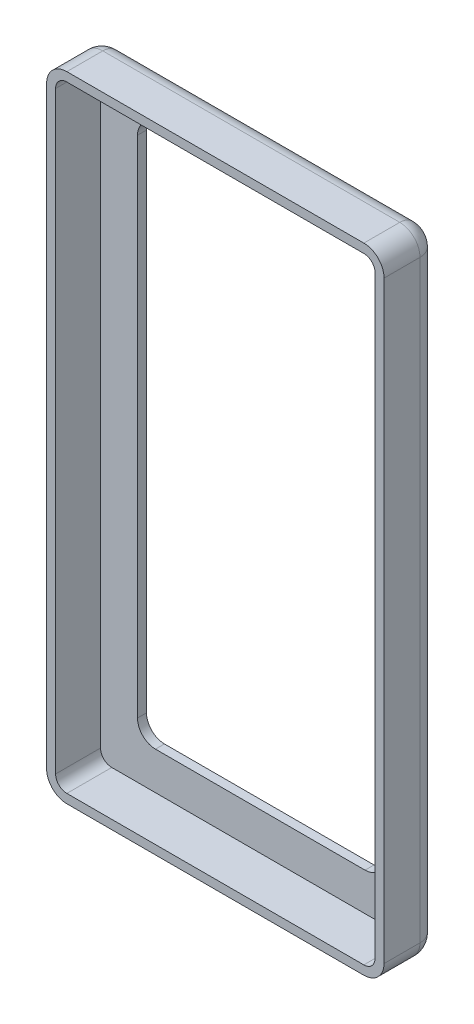
SolidWorks part; units mm, degrees
material "Plastique personnalisé"
ref_plane "Plan de face" through (0, 0, 0) normal (0, 0, 1) x (1, 0, 0)
ref_plane "Plan de dessus" through (0, 0, 0) normal (0, 1, 0) x (1, 0, 0)
ref_plane "Plan de droite" through (0, 0, 0) normal (1, 0, 0) x (0, 0, -1)
sketch "Esquisse1" plane through (0, 0, 0) normal (0, 0, 1) x (1, 0, 0)
  line L0 (-33.5062, 69.5614) -> (42.7461, 69.5614) construction
  line L1 (35.0738, 14.3164) -> (35.0738, 71.5291) construction
  line L2 (-36.0462, -49.8186) -> (-36.0462, -71.5291) construction
  line L3 (-19.7068, -67.5986) -> (-42.7461, -67.5986) construction
  line L4 (-33.5462, -67.5986) -> (32.5738, -67.5986)
  line L5 (-36.0462, -65.0986) -> (-36.0462, 67.0614)
  line L6 (-33.5462, 69.5614) -> (32.5738, 69.5614)
  line L7 (35.0738, -65.0986) -> (35.0738, 67.0614)
  arc A4 (32.5738, -67.5986) -> (35.0738, -65.0986) centre (32.5738, -65.0986) ccw
  arc A5 (-33.5462, -67.5986) -> (-36.0462, -65.0986) centre (-33.5462, -65.0986) cw
  arc A6 (-36.0462, 67.0614) -> (-33.5462, 69.5614) centre (-33.5462, 67.0614) cw
  arc A7 (32.5738, 69.5614) -> (35.0738, 67.0614) centre (32.5738, 67.0614) cw
extrude "Boss.-Extru.1" add sketch "Esquisse1" along normal blind 10
shell "Coque1" thickness 2 removed face at (-0.4862, 0.9814, 10) outward yes
fillet "Congé1" radius 4 8 edges at (37.0738, 0.9814, -2) (35.7558, -68.2806, -2) (-0.4862, -69.5986, -2) (-36.7282, -68.2806, -2) (-38.0462, 0.9814, -2) (-36.7282, 70.2434, -2) (-0.4862, 71.5614, -2) (35.7558, 70.2434, -2)
sketch "Esquisse2" plane through (0, 0, -2) normal (0, 0, -1) x (-1, 0, 0)
  line L0 (-32.9273, 67.415) -> (33.8998, -65.4521) construction
  line L2 (-22.8415, -59.1971) -> (23.814, -59.1971)
  line L3 (-26.8415, -55.1971) -> (-26.8415, 57.1599)
  line L4 (-22.8415, 61.1599) -> (23.814, 61.1599)
  line L5 (27.814, -55.1971) -> (27.814, 57.1599)
  line L6 (-26.8415, -59.1971) -> (27.814, 61.1599) construction
  line L7 (-26.8415, 61.1599) -> (27.814, -59.1971) construction
  arc A0 (-32.5738, 67.5614) -> (-33.0738, 67.0614) centre (-32.5738, 67.0614) ccw construction
  arc A1 (33.5462, -65.5986) -> (34.0462, -65.0986) centre (33.5462, -65.0986) ccw construction
  arc A2 (23.814, -59.1971) -> (27.814, -55.1971) centre (23.814, -55.1971) ccw
  arc A3 (-22.8415, -59.1971) -> (-26.8415, -55.1971) centre (-22.8415, -55.1971) cw
  arc A4 (-26.8415, 57.1599) -> (-22.8415, 61.1599) centre (-22.8415, 57.1599) cw
  arc A5 (23.814, 61.1599) -> (27.814, 57.1599) centre (23.814, 57.1599) cw
  point P8 (0.4862, 0.9814)
  dimension "D1" = 4
extrude "Enlèv. mat.-Extru.1" cut sketch "Esquisse2" against normal blind 10
